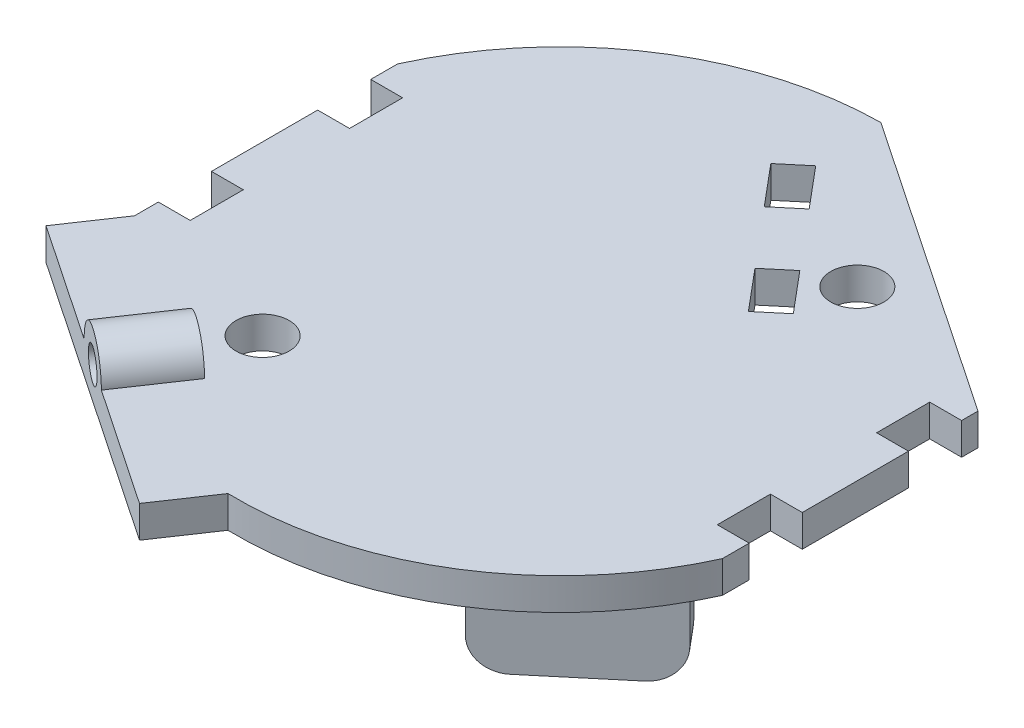
SolidWorks part; units mm, degrees
ref_plane "Alzado" through (0, 0, 0) normal (0, 0, 1) x (1, 0, 0)
ref_plane "Planta" through (0, 0, 0) normal (0, 1, 0) x (1, 0, 0)
ref_plane "Vista lateral" through (0, 0, 0) normal (1, 0, 0) x (0, 0, -1)
sketch "Croquis1" plane through (0, 0, 0) normal (0, 1, 0) x (1, 0, 0)
  circle A0 centre (0, 0) radius 30.5
extrude "Saliente-Extruir1" add sketch "Croquis1" along normal blind 3
sketch "Croquis5" plane through (0, 3, 0) normal (0, 1, 0) x (1, 0, 0)
  line L0 (0, 0) -> (0, 10)
  line L1 (28.8141, -5) -> (30.0874, -5)
  line L2 (28.8141, 5) -> (30.0874, 5)
  line L3 (-24.8141, 10) -> (-28.8141, 10)
  line L4 (24.8141, -5) -> (24.8141, -10)
  line L5 (-24.8141, -10) -> (-28.8141, -10)
  line L6 (24.8141, -5) -> (28.8141, -5)
  line L7 (24.8141, 5) -> (24.8141, 10)
  line L8 (-24.8141, 5) -> (-28.8141, 5)
  line L9 (-24.8141, 5) -> (-24.8141, 10)
  line L10 (-24.8141, -5) -> (-28.8141, -5)
  line L11 (-24.8141, -5) -> (-24.8141, -10)
  line L12 (24.8141, 5) -> (28.8141, 5)
  line L13 (24.8141, -10) -> (28.8141, -10)
  line L14 (24.8141, 10) -> (28.8141, 10)
  line L15 (-28.8141, 5) -> (-30.0874, 5)
  line L16 (-28.8141, -5) -> (-30.0874, -5)
  circle A1 centre (0, 0) radius 30.5 construction
  arc A2 (-28.8141, 10) -> (-30.0874, 5) centre (0, 0) ccw
  arc A3 (28.8141, 10) -> (28.8141, -10) centre (0, 0) cw
  arc A4 (-30.0874, -5) -> (-28.8141, -10) centre (0, 0) ccw
  arc A5 (30.0874, -5) -> (28.8141, -10) centre (0, 0) cw
  arc A6 (28.8141, 10) -> (30.0874, 5) centre (0, 0) cw
  circle M2 centre (0, 0) radius 30.5
extrude "Cortar-Extruir3" cut sketch "Croquis5" against normal blind 4 contours L11 L10 L8 L9 L3 L5 M2 | L15 L8 L9 L3 M2 | L14 L7 L12 L2 M2 | L4 L13 L1 L6 M2 region at (27.1844, 3, 7.3876) region at (27.1844, 3, -7.3876) region at (-27.1844, 3, 7.3876) region at (-27.1844, 3, -7.3876)
sketch "Croquis9" plane through (0, 3, 0) normal (0, 1, 0) x (1, 0, 0)
  line L0 (5.6733, 12.6854) -> (8.8872, 8.8552)
  line L2 (7.9714, 14.6138) -> (11.1854, 10.7835)
  line L3 (-24.8141, -5) -> (-24.8141, -10)
  line L4 (-24.8141, -10) -> (-28.8141, -10)
  line L5 (11.1854, 10.7835) -> (8.8872, 8.8552)
  line L7 (7.9714, 14.6138) -> (5.6733, 12.6854)
  line L11 (-2.1205, 21.9737) -> (1.0934, 18.1435)
  line L12 (0.1776, 23.902) -> (3.3916, 20.0718)
  line L13 (-24.8141, 10) -> (-28.8141, 10)
  line L14 (3.3916, 20.0718) -> (1.0934, 18.1435)
  line L15 (0.1776, 23.902) -> (-2.1205, 21.9737)
  arc A1 (28.8141, 10) -> (-28.8141, 10) centre (0, 0) ccw construction
  arc A5 (-28.8141, -10) -> (28.8141, -10) centre (0, 0) ccw construction
  arc A7 (-28.8141, -10) -> (22.3289, -20.7766) centre (0, 0) ccw
  arc A8 (-28.8141, 10) -> (-8.3073, 29.3469) centre (0, 0) cw
extrude "Cortar-Extruir6" cut sketch "Croquis9" against normal blind 10 contours L2 L7 | L12 L15 L14 region at (8.4293, 3, -11.7345) region at (0.6355, 3, -21.0227)
sketch "Croquis10" plane through (0, 3, 0) normal (0, 1, 0) x (1, 0, 0)
  line L0 (0, 0) -> (12, 0)
  line L1 (12, 0) -> (12, 16)
  line L2 (0, 0) -> (-12, 0)
  line L3 (-12, 0) -> (-12, -16)
  circle A0 centre (12, 16) radius 2.5
  circle A1 centre (-12, -16) radius 2.5
extrude "Cortar-Extruir7" cut sketch "Croquis10" against normal blind 10 contours A0 | A1 region at (10.2822, 3, -17.7178) region at (-10.2822, 3, 14.2822)
sketch "Croquis11" plane through (0, 3, 0) normal (0, 1, 0) x (1, 0, 0)
  line L0 (27.8141, 5) -> (30.0874, 5)
  line L1 (-27.8141, 5) -> (-27.8141, -5)
  line L2 (-24.8141, -5) -> (-30.0874, -5) construction
  line L3 (27.8141, 10) -> (28.8141, 10)
  line L4 (24.8141, 5) -> (30.0874, 5) construction
  line L5 (27.8141, 5) -> (27.8141, -5)
  line L6 (24.8141, -5) -> (30.0874, -5) construction
  line L7 (27.8141, -5) -> (30.0874, -5)
  line L8 (24.8141, 10) -> (28.8141, 10) construction
  line L9 (27.8141, 10) -> (27.8141, 12.5151)
  line L10 (27.8141, -10) -> (28.8141, -10)
  line L11 (24.8141, -10) -> (28.8141, -10) construction
  line L12 (27.8141, -10) -> (27.8141, -12.5151)
  line L13 (-28.8141, -10) -> (-27.8141, -10)
  line L14 (-24.8141, 10) -> (-28.8141, 10) construction
  line L15 (-27.8141, 10) -> (-27.8141, 12.5151)
  line L16 (-27.8141, -5) -> (-30.0874, -5)
  line L17 (-27.8141, -10) -> (-27.8141, -12.5151)
  line L18 (-27.8141, 10) -> (-28.8141, 10)
  line L19 (-30.0874, 5) -> (-27.8141, 5)
  arc A0 (28.8141, 10) -> (-28.8141, 10) centre (0, 0) ccw construction
  arc A1 (-28.8141, -10) -> (28.8141, -10) centre (0, 0) ccw construction
  arc A2 (28.8141, 10) -> (-28.8141, 10) centre (0, 0) ccw construction
  arc A3 (30.0874, -5) -> (30.0874, 5) centre (0, 0) ccw
  arc A4 (28.8141, -10) -> (27.8141, -12.5151) centre (0, 0) cw
  arc A5 (28.8141, 10) -> (27.8141, 12.5151) centre (0, 0) ccw
  arc A6 (-30.0874, -5) -> (-30.0874, 5) centre (0, 0) cw
  arc A7 (-27.8141, 12.5151) -> (-28.8141, 10) centre (0, 0) ccw
  arc A8 (-28.8141, -10) -> (-27.8141, -12.5151) centre (0, 0) ccw
  arc M11 (28.8141, 10) -> (-28.8141, 10) centre (0, 0) ccw
  line M17 (-24.8141, 5) -> (-30.0874, 5)
  arc M18 (-30.0874, 5) -> (-30.0874, -5) centre (0, 0) ccw
  line M19 (-30.0874, -5) -> (-24.8141, -5)
  arc M21 (-28.8141, -10) -> (28.8141, -10) centre (0, 0) ccw
  line M22 (28.8141, -10) -> (24.8141, -10)
  line M24 (24.8141, -5) -> (30.0874, -5)
  arc M25 (30.0874, -5) -> (30.0874, 5) centre (0, 0) ccw
  line M26 (30.0874, 5) -> (24.8141, 5)
  line M28 (24.8141, 10) -> (28.8141, 10)
  line M54 (-24.8141, -10) -> (-28.8141, -10)
  line M56 (-28.8141, 10) -> (-24.8141, 10)
extrude "Cortar-Extruir8" cut sketch "Croquis11" against normal blind 3 contours L17 M54 M21 | L1 M17 M18 M19 | L15 M56 M11 | L12 M22 M21 | L5 M26 M24 M25 | L9 M28 M11 region at (29.0914, 3, 0) region at (-29.0914, 3, 0) region at (28.1547, 3, -10.8559) region at (-28.1547, 3, -10.8559) region at (-28.1547, 3, 10.8559) region at (28.1547, 3, 10.8559)
sketch "Croquis13" plane through (0, 0, 0) normal (0, -1, 0) x (1, 0, 0)
  line L0 (-6.8167, 4.322) -> (-19.6724, -10.9989)
  line L1 (-19.6724, -10.9989) -> (-17.3743, -12.9273)
  line L2 (-17.3743, -12.9273) -> (-4.5186, 2.3936)
  line L3 (-4.5186, 2.3936) -> (-6.8167, 4.322)
  line L4 (21.5273, 8.9312) -> (23.4556, 11.2293)
  line L5 (23.4556, 11.2293) -> (11.965, 20.8711)
  line L6 (11.965, 20.8711) -> (10.0366, 18.573)
  line L7 (10.0366, 18.573) -> (21.5273, 8.9312)
extrude "Saliente-Extruir2" add sketch "Croquis13" along normal blind 10
fillet "Redondeo1" radius 3 4 edges at (11.0008, -10, 19.7221) (22.4915, -10, 10.0802) (-5.6676, -10, 3.3578) (-18.5234, -10, -11.9631)
fillet "Redondeo2" radius 1 6 edges at (17.7103, 0, 16.0502) (11.0008, 0, 19.7221) (-5.6676, 0, 3.3578) (-13.2446, 0, -3.3385) (22.4915, 0, 10.0802) (-18.5234, 0, -11.9631)
sketch "Croquis14" plane through (0, 3, 0) normal (0, 1, 0) x (1, 0, 0)
  line L3 (29.8013, 10.2046) -> (-1.7022, 31.454)
  circle A0 centre (0, 0) radius 31.5
  line M12 (27.8141, 10) -> (27.8141, 12.5151)
  arc M13 (27.8141, 12.5151) -> (-27.8141, 12.5151) centre (0, 0) ccw
extrude "Cortar-Extruir9" cut sketch "Croquis14" against normal blind 3 contours L3 M12 M13 region at (15.2326, 3, -22.6507)
sketch "Croquis15" plane through (0, 3, 0) normal (0, 1, 0) x (1, 0, 0)
  line L0 (-0.2859, 30.4987) -> (27.8141, 11.545)
  line L1 (-0.2859, 30.4987) -> (-28.711, -11.6433)
  line L2 (27.8141, 11.545) -> (-0.6111, -30.5969)
  line L3 (-28.711, -11.6433) -> (-0.6111, -30.5969)
  line L4 (-27.8141, -12.5151) -> (-27.8141, -12.2483)
  line L5 (-27.8141, -10) -> (-27.8141, -12.5151) construction
  arc A0 (-0.6111, -30.5969) -> (-27.8141, -12.5151) centre (0.1659, 0.0754) cw
extrude "Cortar-Extruir10" cut sketch "Croquis15" against normal blind 10 contours L3 region at (-15.3795, 3, 22.9776) body kept at (10.0366, -1, 18.573)
sketch "Croquis16" plane through (-14.3756, 0, 21.3127) normal (-0.5592, 0, 0.829) x (0.829, 0, 0.5592)
  line L1 (-16.2097, 3) -> (16.4123, 3)
  line L2 (-16.2097, 3) -> (-16.2097, 0)
  line L3 (-16.2097, 0) -> (16.4123, 0)
  line L4 (16.4123, 3) -> (16.4123, 0)
extrude "Saliente-Extruir3" add sketch "Croquis16" along normal blind 6
sketch "Croquis17" plane through (-17.7307, 0, 26.2869) normal (-0.5592, 0, 0.829) x (0.829, 0, 0.5592)
  line L0 (16.4123, 3) -> (-16.2097, 3) construction
  circle A0 centre (0.1013, 3) radius 3
extrude "Saliente-Extruir4" add sketch "Croquis17" against normal blind 7
sketch "Croquis18" plane through (-17.7307, 0, 26.2869) normal (-0.5592, 0, 0.829) x (0.829, 0, 0.5592)
  circle A0 centre (0.1013, 3) radius 1.5
extrude "Cortar-Extruir11" cut sketch "Croquis18" against normal blind 6
